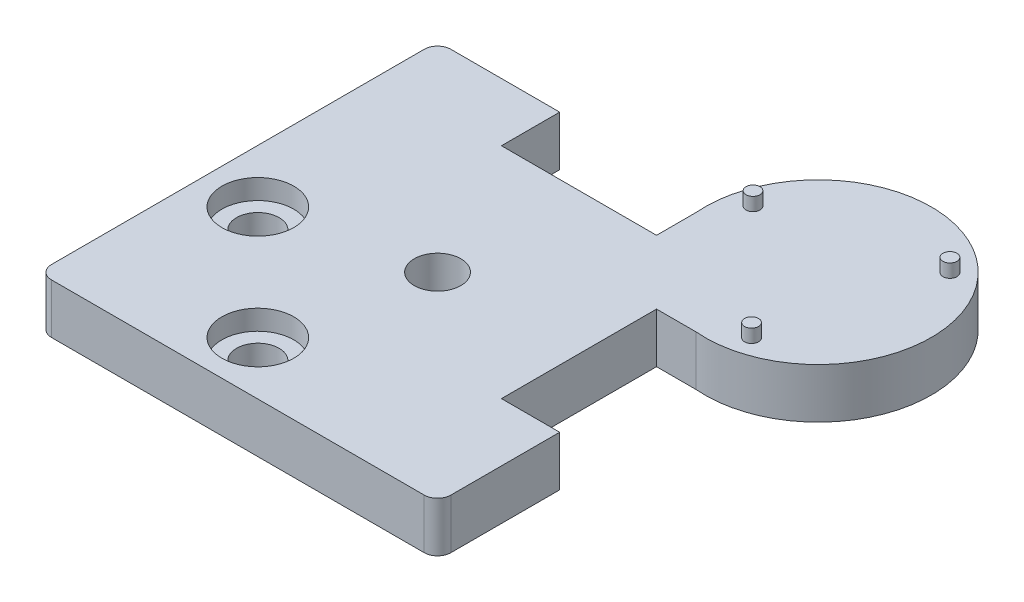
SolidWorks part; units mm, degrees
ref_plane "Front Plane" through (0, 0, 0) normal (0, 0, 1) x (1, 0, 0)
ref_plane "Top Plane" through (0, 0, 0) normal (0, 1, 0) x (1, 0, 0)
ref_plane "Right Plane" through (0, 0, 0) normal (1, 0, 0) x (0, 0, -1)
sketch "Sketch1" plane through (0, 0, 0) normal (0, 1, 0) x (1, 0, 0)
  line L1 (-38.1, 38.1) -> (38.1, 38.1)
  line L2 (-38.1, 38.1) -> (-38.1, -38.1)
  line L3 (-38.1, -38.1) -> (38.1, -38.1)
  line L4 (38.1, 38.1) -> (38.1, -38.1)
  line L5 (-38.1, 38.1) -> (38.1, -38.1) construction
  line L6 (-38.1, -38.1) -> (38.1, 38.1) construction
  point P0 (0, 0)
  dimension "D1" = 76.2
extrude "Boss-Extrude1" add sketch "Sketch1" along normal blind 9.525
sketch "Sketch6" plane through (0, 0, 0) normal (0, 1, 0) x (1, 0, 0)
  line L0 (38.1, 38.1) -> (-38.1, 38.1) construction
  line L1 (-38.1, 38.1) -> (-38.1, -38.1) construction
  line L2 (38.1, -38.1) -> (38.1, 38.1) construction
  line L3 (-38.1, -38.1) -> (38.1, -38.1) construction
  circle A0 centre (-28.575, 28.575) radius 3.81
  circle A1 centre (28.575, -28.575) radius 3.81
  dimension "D2" = 7.62
  dimension "D1" = 9.525
  dimension "D3" = 9.525
  dimension "D4" = 9.525
  dimension "D5" = 9.525
extrude "Cut-Extrude2" cut sketch "Sketch6" along direction (0, 1, 0) on the side of the normal blind 2.54 draft 30
sketch "Sketch7" plane through (0, 0, 0) normal (0, 1, 0) x (1, 0, 0)
  line L2 (-38.1, 38.1) -> (-38.1, -38.1) construction
  line L3 (-38.1, -38.1) -> (38.1, -38.1) construction
  circle A0 centre (-27.94, -27.94) radius 4.445
  dimension "D3" = 8.89
  dimension "D2" = 10.16
  dimension "D1" = 10.16
sketch "Sketch12" plane through (0, 9.525, 0) normal (0, 1, 0) x (1, 0, 0)
  line L2 (-38.1, -38.1) -> (38.1, -38.1) construction
  line L3 (-38.1, 38.1) -> (-38.1, -38.1) construction
  circle A0 centre (-27.94, -6.35) radius 4.064
  circle A1 centre (-6.35, -27.94) radius 4.064
  dimension "D2" = 10.16
  dimension "D3" = 8.128
  dimension "D4" = 31.75
  dimension "D5" = 10.16
  dimension "D1" = 31.75
extrude "Cut-Extrude4" cut sketch "Sketch12" against normal up to next
sketch "Sketch13" plane through (0, 9.525, 0) normal (0, -1, 0) x (1, 0, 0)
  circle A6 centre (-27.94, 6.35) radius 6.858
  circle A9 centre (-6.35, 27.94) radius 6.858
  dimension "D1" = 13.716
  dimension "D2" = 13.716
extrude "Cut-Extrude7" cut sketch "Sketch13" along normal blind 3.81
extrude "Cut-Extrude8" cut sketch "Sketch7" along normal blind 3.81 draft 45
ref_axis "Axis1" through (-6.35, -9.5852, 27.94) along (0, 1, 0)
ref_axis "Axis2" through (-27.94, -15.4165, 6.35) along (0, 1, 0)
sketch "Sketch15" plane through (0, 9.525, 0) normal (0, 1, 0) x (1, 0, 0)
  circle A4 centre (0, 0) radius 4.445
  dimension "D1" = 8.89
extrude "Cut-Extrude9" cut sketch "Sketch15" against normal up to next
fillet "Fillet1" radius 2.54 4 edges at (38.1, 4.7625, -38.1) (38.1, 4.7625, 38.1) (-38.1, 4.7625, 38.1) (-38.1, 4.7625, -38.1)
sketch "Sketch16" plane through (0, 0, 0) normal (0, -1, 0) x (1, 0, 0)
  line L0 (0, 0) -> (0, -38.1) construction
  line L1 (35.56, -38.1) -> (-35.56, -38.1) construction
  line L2 (0, 0) -> (38.1, 0) construction
  line L3 (38.1, 35.56) -> (38.1, -35.56) construction
  line L4 (-14.7955, -38.1) -> (14.7955, -38.1)
  line L5 (14.7955, -38.1) -> (14.7955, -26.9875)
  line L6 (14.7955, -26.9875) -> (-14.7955, -26.9875)
  line L7 (-14.7955, -26.9875) -> (-14.7955, -38.1)
  line L8 (38.1, -14.7955) -> (38.1, 14.7955)
  line L9 (38.1, 14.7955) -> (26.9875, 14.7955)
  line L10 (26.9875, 14.7955) -> (26.9875, -14.7955)
  line L11 (26.9875, -14.7955) -> (38.1, -14.7955)
  point P11 (0, -38.1)
  point P16 (38.1, 0)
  dimension "D1" = 29.591
  dimension "D2" = 29.591
  dimension "D3" = 11.1125
  dimension "D4" = 11.1125
extrude "Cut-Extrude10" cut sketch "Sketch16" against normal up to next
sketch "Sketch17" plane through (0, 9.525, 0) normal (0, 1, 0) x (1, 0, 0)
  circle A0 centre (36.3113, 36.3113) radius 21.59
  point P5 (36.3113, 36.3113)
  dimension "D1" = 43.18
extrude "Boss-Extrude2" add sketch "Sketch17" against normal up to surface (9.525 mm away) up to face at (0, 0, 4.445)
sketch "Sketch18" plane through (0, 9.525, 0) normal (0, 1, 0) x (1, 0, 0)
  line L0 (-38.1, 35.56) -> (-38.1, -35.56) construction
  circle A0 centre (19.1663, 41.0207) radius 1.3335
  circle A2 centre (48.9622, 48.8046) radius 1.3335
  circle A3 centre (40.8053, 19.1086) radius 1.3335
  point P10 (36.3113, 36.3113)
  dimension "D1" = 2.667
  dimension "D2" = 17.78
  dimension "D4" = 57.2663
  dimension "D5" = 74.4113
  dimension "D6" = 78.9053
  dimension "D3" = 3
extrude "Boss-Extrude3" add sketch "Sketch18" along normal blind 2.54
